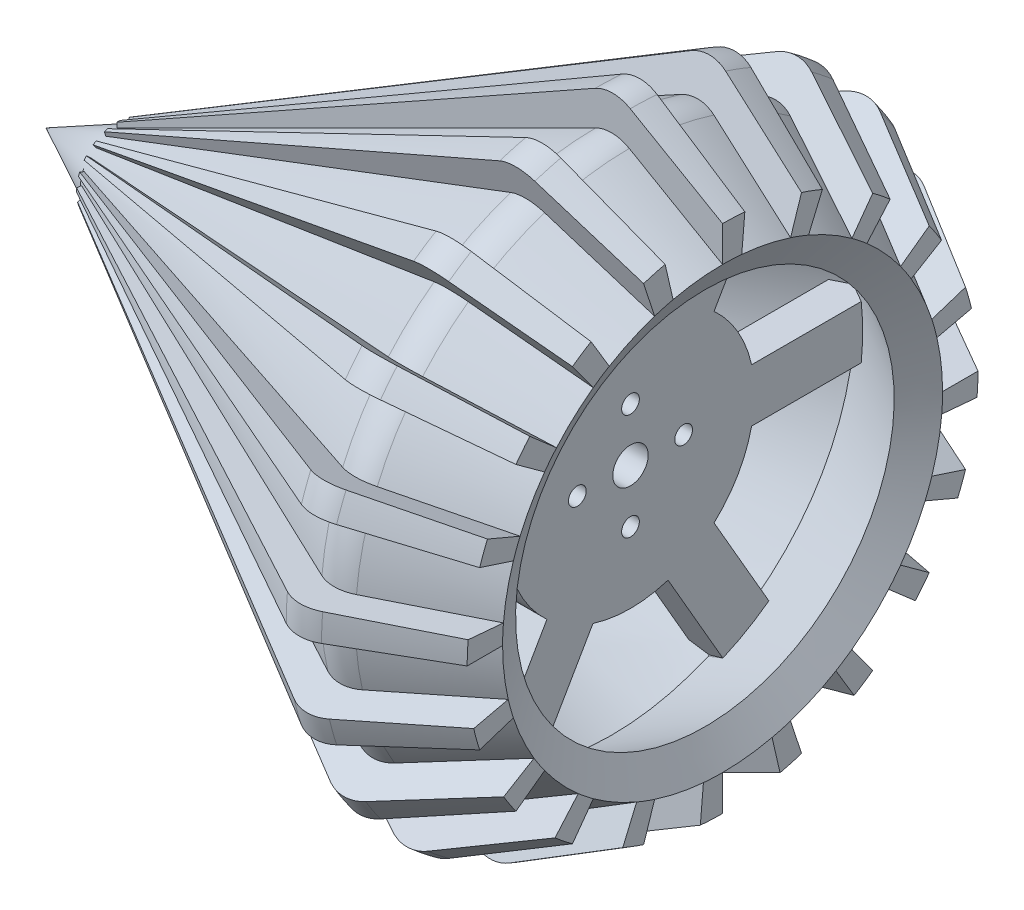
SolidWorks part; units mm, degrees
ref_plane "Front Plane" through (0, 0, 0) normal (0, 0, 1) x (1, 0, 0)
ref_plane "Top Plane" through (0, 0, 0) normal (0, 1, 0) x (1, 0, 0)
ref_plane "Right Plane" through (0, 0, 0) normal (1, 0, 0) x (0, 0, -1)
sketch "Sketch2" plane through (0, 0, 0) normal (0, 0, 1) x (1, 0, 0)
  line L0 (33.4615, 0) -> (-190.5, 0) construction
  line L1 (-190.5, 0) -> (-263.4708, 0) construction
  line L5 (39.3699, 78.8698) -> (0, 101.6)
  line L6 (0, 101.6) -> (-203.2, 0)
  line L8 (33.0199, 67.8713) -> (-0.4322, 87.1849)
  line L9 (-0.4322, 87.1849) -> (-174.8019, 0)
  line L10 (-203.2, 0) -> (-174.8019, 0)
  line L11 (-0.4322, 87.1849) -> (-197.5204, -11.3592) construction
  line L12 (39.3699, 78.8698) -> (33.0199, 67.8713)
  line L13 (0, 0) -> (0, 134.0479) construction
  dimension "D1" = 101.6
  dimension "D2" = 203.2
  dimension "D3" = 12.7
  dimension "D4" = 30
revolve "Revolve1" add sketch "Sketch2" angle 360 about L0
sketch "Sketch3" plane through (0, 0, 0) normal (0, 0, 1) x (1, 0, 0)
  line L0 (-177.8, 14.4619) -> (0, 114.3)
  line L1 (0, 114.3) -> (39.3699, 91.5698)
  line L2 (39.3699, 91.5698) -> (39.3699, 78.8698)
  line L3 (39.3699, 78.8698) -> (0, 101.6)
  line L4 (0, 101.6) -> (-177.8, 12.7)
  line L5 (0, 0) -> (0, 133.0618) construction
  line L6 (95.9453, 0) -> (-261.7553, 0) construction
  line L7 (-177.8, 14.4619) -> (-177.8, 12.7)
  line L8 (0, 101.6) -> (-203.2, 0) construction
  dimension "D1" = 114.3
  dimension "D2" = 177.8
  dimension "D3" = 2.75
revolve "Revolve8" add sketch "Sketch3" angle 5 about L6
ref_axis "Axis1" through (-279.6403, 0, 0) along (1, 0, 0)
pattern_circular "CirPattern3" count 20 over 360 about axis through (-279.6403, 0, 0) along (1, 0, 0) of bodies 102
combine bodies "Combine1" bodies to combine 121 102 103 104 105 101 106 107 108 109 110 111 112 113 114 115 117 116 118 119 120
fillet "Fillet2" radius 12.7 40 edges at (0, 71.1534, 89.4521) (0, 50.0302, 88.4281) (0, 40.0287, 107.0616) (0, 20.2558, 99.5603) (0, 4.9857, 114.1912) (0, -11.5014, 100.9469) (0, -30.5453, 110.143) (0, -42.1328, 92.4521) (0, -63.0864, 95.3131) (0, -68.64, 74.9074) (0, -89.4521, 71.1534) (0, -88.4281, 50.0302) (0, -107.0616, 40.0287) (0, -99.5603, 20.2558) (0, -114.1912, 4.9857) (0, -100.9469, -11.5014) (0, -110.143, -30.5453) (0, -92.4521, -42.1328) (0, -95.3131, -63.0864) (0, -74.9074, -68.64) (0, -71.1534, -89.4521) (0, -50.0302, -88.4281) (0, -40.0287, -107.0616) (0, -20.2558, -99.5603) (0, -4.9857, -114.1912) (0, 11.5014, -100.9469) (0, 30.5453, -110.143) (0, 42.1328, -92.4521) (0, 63.0864, -95.3131) (0, 68.64, -74.9074) (0, 89.4521, -71.1534) (0, 88.4281, -50.0302) (0, 107.0616, -40.0287) (0, 99.5603, -20.2558) (0, 100.9469, 11.5014) (0, 92.4521, 42.1328) (0, 74.9074, 68.64) (0, 95.3131, 63.0864) (0, 110.143, 30.5453) (0, 114.1912, -4.9857)
sketch "Sketch4" plane through (0, 0, 0) normal (1, 0, 0) x (0, 0, -1)
  line L0 (0, 55.155) -> (0, -59.58) construction
  line L1 (29.9576, -32.8381) -> (55.8739, -77.7264)
  line L2 (-57.8416, 0) -> (54.3648, 0) construction
  line L3 (43.4175, 9.525) -> (95.25, 9.525)
  line L5 (43.4175, -9.525) -> (95.25, -9.525)
  line L6 (95.25, 9.525) -> (95.25, -9.525)
  line L7 (13.4598, -42.3631) -> (39.3761, -87.2514)
  line L8 (55.8739, -77.7264) -> (39.3761, -87.2514)
  line L9 (-13.4598, -42.3631) -> (-39.3761, -87.2514)
  line L10 (-29.9576, -32.8381) -> (-55.8739, -77.7264)
  line L11 (-39.3761, -87.2514) -> (-55.8739, -77.7264)
  line L12 (-43.4175, -9.525) -> (-95.25, -9.525)
  line L13 (-43.4175, 9.525) -> (-95.25, 9.525)
  line L14 (-95.25, -9.525) -> (-95.25, 9.525)
  line L15 (-29.9576, 32.8381) -> (-55.8739, 77.7264)
  line L16 (-13.4598, 42.3631) -> (-39.3761, 87.2514)
  line L17 (-55.8739, 77.7264) -> (-39.3761, 87.2514)
  line L18 (13.4598, 42.3631) -> (39.3761, 87.2514)
  line L19 (29.9576, 32.8381) -> (55.8739, 77.7264)
  line L20 (39.3761, 87.2514) -> (55.8739, 77.7264)
  arc A0 (43.4175, 9.525) -> (29.9576, 32.8381) centre (0, 0) ccw
  circle A1 centre (0, 0) radius 6.35
  circle A2 centre (0, 19.05) radius 3.175
  circle A3 centre (19.05, 0) radius 3.175
  circle A4 centre (0, -19.05) radius 3.175
  circle A5 centre (-19.05, 0) radius 3.175
  arc A6 (13.4598, 42.3631) -> (-13.4598, 42.3631) centre (0, 0) ccw
  arc A7 (-29.9576, 32.8381) -> (-43.4175, 9.525) centre (0, 0) ccw
  arc A8 (-43.4175, -9.525) -> (-29.9576, -32.8381) centre (0, 0) ccw
  arc A9 (-13.4598, -42.3631) -> (13.4598, -42.3631) centre (0, 0) ccw
  arc A10 (29.9576, -32.8381) -> (43.4175, -9.525) centre (0, 0) ccw
  dimension "D1" = 88.9
  dimension "D6" = 6.35
  dimension "D7" = 6.35
  dimension "D8" = 6.35
  dimension "D9" = 6.35
  dimension "D10" = 12.7
  dimension "D2" = 19.05
  dimension "D3" = 19.05
  dimension "D4" = 19.05
  dimension "D5" = 19.05
  dimension "D12" = 9.525
  dimension "D11" = 19.05
  dimension "D13" = 95.25
  dimension "D14" = 6
extrude "Boss-Extrude1" add sketch "Sketch4" along normal mid plane 12.7
ref_plane "Plane1" through (-127, 0, 0) normal (1, 0, 0) x (0, 0, -1)
sketch "Sketch5" plane through (-127, 0, 0) normal (1, 0, 0) x (0, 0, -1)
  line L0 (-38.9608, 0) -> (64.0175, 0) construction
  line L1 (24.5934, 6.35) -> (44.45, 6.35)
  line L3 (24.5934, -6.35) -> (44.45, -6.35)
  line L4 (44.45, 6.35) -> (44.45, -6.35)
  line L5 (17.796, -18.1235) -> (27.7243, -35.3198)
  line L6 (0, -38.5344) -> (0, 35.4192) construction
  line L7 (27.7243, -35.3198) -> (16.7257, -41.6698)
  line L8 (6.7975, -24.4735) -> (16.7257, -41.6698)
  line L9 (-6.7975, -24.4735) -> (-16.7257, -41.6698)
  line L10 (-16.7257, -41.6698) -> (-27.7243, -35.3198)
  line L11 (-17.796, -18.1235) -> (-27.7243, -35.3198)
  line L12 (-24.5934, -6.35) -> (-44.45, -6.35)
  line L13 (-44.45, -6.35) -> (-44.45, 6.35)
  line L14 (-24.5934, 6.35) -> (-44.45, 6.35)
  line L15 (-17.796, 18.1235) -> (-27.7243, 35.3198)
  line L16 (-27.7243, 35.3198) -> (-16.7257, 41.6698)
  line L17 (-6.7975, 24.4735) -> (-16.7257, 41.6698)
  line L18 (6.7975, 24.4735) -> (16.7257, 41.6698)
  line L19 (16.7257, 41.6698) -> (27.7243, 35.3198)
  line L20 (17.796, 18.1235) -> (27.7243, 35.3198)
  arc A0 (24.5934, 6.35) -> (17.796, 18.1235) centre (0, 0) ccw
  circle A1 centre (0, 0) radius 6.35
  arc A2 (6.7975, 24.4735) -> (-6.7975, 24.4735) centre (0, 0) ccw
  arc A3 (-17.796, 18.1235) -> (-24.5934, 6.35) centre (0, 0) ccw
  arc A4 (-24.5934, -6.35) -> (-17.796, -18.1235) centre (0, 0) ccw
  arc A5 (-6.7975, -24.4735) -> (6.7975, -24.4735) centre (0, 0) ccw
  arc A6 (17.796, -18.1235) -> (24.5934, -6.35) centre (0, 0) ccw
  point P33 (0, 0)
  dimension "D1" = 50.8
  dimension "D2" = 12.7
  dimension "D3" = 12.7
  dimension "D4" = 6.35
  dimension "D5" = 19.8566
extrude "Boss-Extrude2" add sketch "Sketch5" along normal mid plane 12.7 separate body
sketch "Sketch6" plane through (0, 0, 0) normal (0, 0, 1) x (1, 0, 0)
  line L0 (-180.0281, 11.586) -> (-92.0527, 53.6678)
  line L1 (-177.8, 12.7) -> (-203.2, 0) construction
  line L2 (-6.3054, 94.9393) -> (-177.8, 12.3962) construction
  line L3 (-92.0527, 53.6678) -> (-98.5511, 67.2532)
  line L4 (-98.5511, 67.2532) -> (-180.0281, 28.2798)
  line L5 (-180.0281, 28.2798) -> (-180.0281, 11.586)
revolve "Cut-Revolve2" cut sketch "Sketch6" angle 360 about axis through (-279.6403, 0, 0) along (1, 0, 0)
equation "\"boltSpacing\"=0.75"
equation "\"D2@Sketch4\"=\"boltSpacing\""
equation "\"D3@Sketch4\"=\"boltSpacing\""
equation "\"D4@Sketch4\"=\"boltSpacing\""
equation "\"D5@Sketch4\"=\"boltSpacing\""
equation "\"boltSizing\"=0.25"
equation "\"D6@Sketch4\"=\"boltSizing\""
equation "\"D7@Sketch4\"=\"boltSizing\""
equation "\"D8@Sketch4\"=\"boltSizing\""
equation "\"D9@Sketch4\"=\"boltSizing\""
equation "\"shaftSizing\"=0.5"
equation "\"D2@Sketch5\"=\"shaftSizing\""
